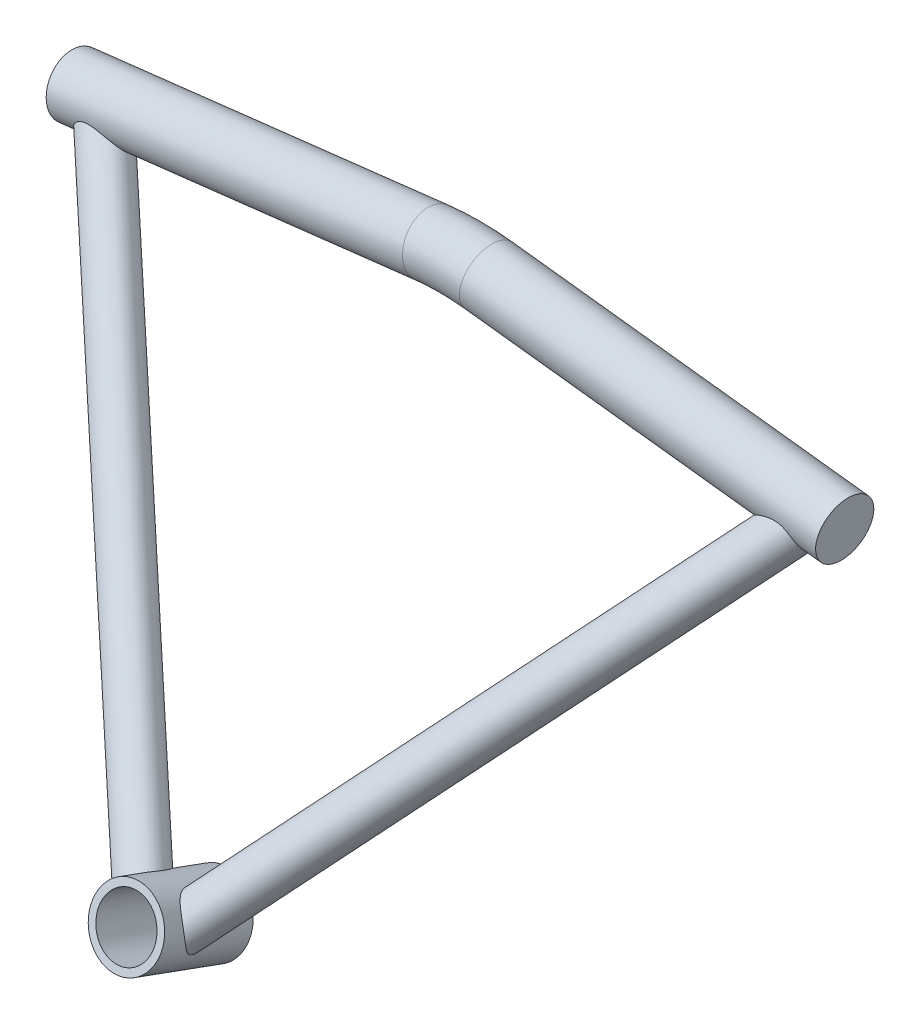
SolidWorks part; units mm, degrees
material "AISI 4130 Steel, normalized at 870C"
ref_plane "Front Plane" through (0, 0, 0) normal (0, 0, 1) x (1, 0, 0)
ref_plane "Top Plane" through (0, 0, 0) normal (0, 1, 0) x (1, 0, 0)
ref_plane "Right Plane" through (0, 0, 0) normal (1, 0, 0) x (0, 0, -1)
sketch "Sketch3" plane through (0, 0, 0) normal (0, 1, 0) x (1, 0, 0)
  line L0 (-5.08, -6.35) -> (5.08, -6.35) construction
  line L2 (0, -88.2205) -> (0, 88.2205) construction
  line L3 (5.08, 0) -> (-5.08, 0) construction
  dimension "D1" = 5.08
  dimension "D2" = 10.16
  dimension "D3" = 6.35
  dimension "D4" = 10.16
  dimension "D5" = 5.08
ref_plane "Plane1" through (0, 3.0807, 3.9431) normal (0, 0.6157, 0.788) x (1, 0, 0)
ref_plane "Plane3" through (0, 0, 0) normal (0, 0.342, 0.9397) x (-1, 0, 0)
sketch "Sketch1" plane through (0, 0, 0) normal (0, 0.342, 0.9397) x (1, 0, 0)
  circle A0 centre (0, 0) radius 15.875
  dimension "D1" = 31.75
extrude "Boss-Extrude1" add sketch "Sketch1" along normal mid plane 41.402 contours A0
sketch "Sketch4" plane through (0, 3.0807, 3.9431) normal (0, 0.6157, 0.788) x (1, 0, 0)
  line L0 (-5.08, -3.9095) -> (-156.596, 212.4778)
  line L2 (0, -90.5202) -> (0, 90.5202) construction
  dimension "D2" = 35
  dimension "D3" = 264.16
sweep "Sweep1" add path "Sketch4" circular profile diameter 19.05 parameters "D3"=19.05
sketch "Sketch15" plane through (0, 3.0807, 3.9431) normal (0, 0.6157, 0.788) x (1, 0, 0)
  line L0 (5.08, -3.9095) -> (156.596, 212.4778)
  line L1 (0, -90.5202) -> (0, 90.5202) construction
  dimension "D1" = 264.16
  dimension "D2" = 35
sweep "Sweep2" add path "Sketch15" circular profile diameter 19.05 parameters "D3"=19.05
sketch "Sketch36" plane through (-151.3504, 170.3291, -133.0757) normal (-0.5736, 0.6455, -0.5043) x (0.819, 0.4396, -0.3688)
  circle A0 centre (-6.5025, -4.8747) radius 7.9375
  dimension "D1" = 15.875
extrude "Cut-Extrude2" cut sketch "Sketch36" against normal up to surface (274.2555 mm away) up to face at (15.2605, -2.6747, 5.4407)
sketch "Sketch37" plane through (151.3504, 170.3291, -133.0757) normal (0.5736, 0.6455, -0.5043) x (0.819, -0.4396, 0.3688)
  circle A0 centre (6.5025, -4.8747) radius 7.9375
  dimension "D1" = 15.875
extrude "Cut-Extrude3" cut sketch "Sketch37" against normal up to surface (249.7225 mm away) up to face at (10.5431, -6.1556, 17.7886)
sketch "Sketch77" plane through (0, 7.0802, 19.4526) normal (0, 0.342, 0.9397) x (1, 0, 0)
  circle A1 centre (0, 0) radius 15.875
extrude "Boss-Extrude2" add sketch "Sketch77" against normal up to surface (41.402 mm away) up to face at (0, -21.9978, -14.023)
sketch "Sketch2" plane through (0, -7.0802, -19.4526) normal (0, -0.342, -0.9397) x (-1, 0, 0)
  circle A0 centre (0, 0) radius 12.7
  dimension "D1" = 25.4
extrude "Cut-Extrude1" cut sketch "Sketch2" against normal up to next
ref_plane "Plane2" through (0, 0, -127) normal (0, 0, 1) x (1, 0, 0)
sketch "Sketch40" plane through (-106.934, 0, -127) normal (0, 0, 1) x (1, 0, 0)
  line L2 (106.934, -90.5202) -> (106.934, 90.5202) construction
  line L3 (94.4475, 187.994) -> (-61.9654, 169.6922)
  line L4 (119.4205, 187.994) -> (275.8334, 169.6922)
  arc A0 (94.4475, 187.994) -> (119.4205, 187.994) centre (106.934, 81.28) cw
  point P0 (106.934, 188.722)
  point P4 (0, 0)
  point P7 (106.934, 188.722)
  point P9 (0, 0)
  point P12 (0, 0)
  point P13 (0, 0)
  point P14 (0, 0)
  point P15 (0, 0)
  point P16 (0, 0)
  point P17 (106.934, 162.0535)
  point P18 (106.934, 162.0535)
  point P19 (0, 0)
  point P20 (0, 0)
  point P21 (0, 0)
  dimension "D1" = 157.48
  dimension "D3" = 107.442
  dimension "D2" = 157.48
  dimension "D4" = 7.6
  dimension "D5" = 107.442
sweep "Sweep3" add path "Sketch40" circular profile diameter 25.4 parameters "D3"=25.4
